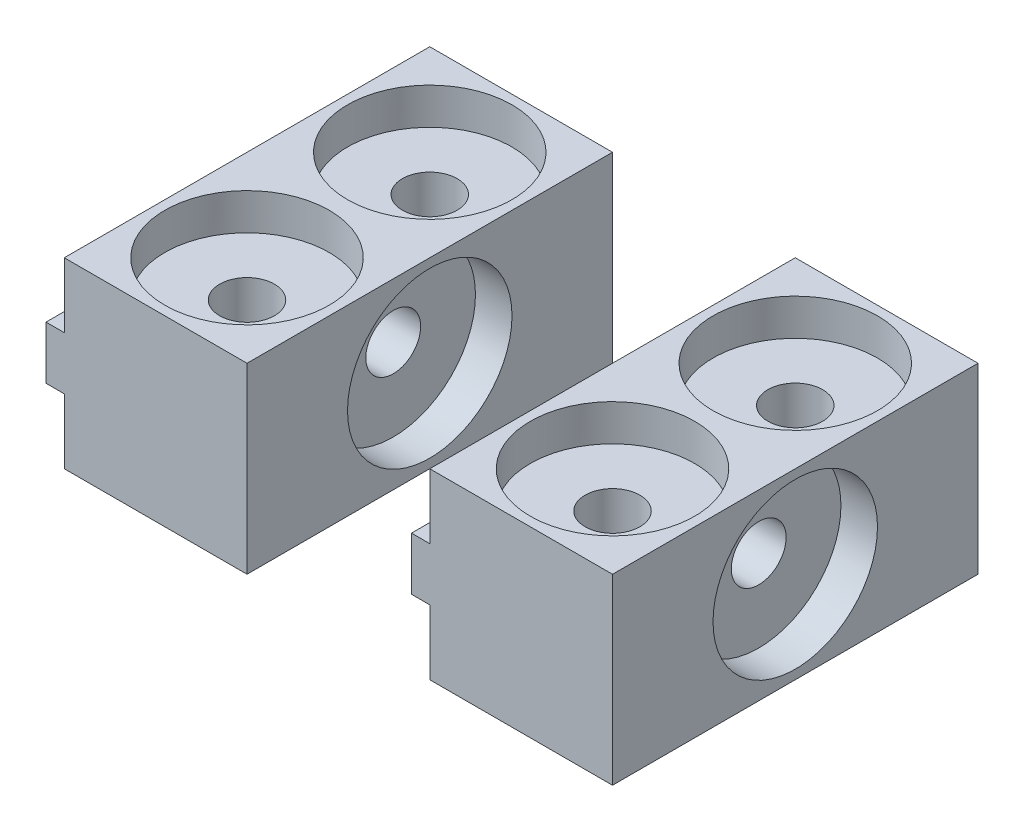
SolidWorks part; units mm, degrees
ref_plane "Front Plane" through (0, 0, 0) normal (0, 0, 1) x (1, 0, 0)
ref_plane "Top Plane" through (0, 0, 0) normal (0, 1, 0) x (1, 0, 0)
ref_plane "Right Plane" through (0, 0, 0) normal (1, 0, 0) x (0, 0, -1)
sketch "Sketch1" plane through (0, 0, 0) normal (0, 0, 1) x (1, 0, 0)
  line L0 (-10, 0) -> (-10, -3.55)
  line L1 (-10, -3.55) -> (-11, -3.55)
  line L2 (-11, -3.55) -> (-11, -6.45)
  line L3 (-11, -6.45) -> (-10, -6.45)
  line L4 (-10, -6.45) -> (-10, -10)
  line L5 (-10, -10) -> (0, -10)
  line L8 (0, -10) -> (0, 0)
  line L9 (0, 0) -> (-10, 0)
  dimension "D1" = 10
  dimension "D2" = 1
  dimension "D3" = 2.9
  dimension "D4" = 10
extrude "Boss-Extrude1" add sketch "Sketch1" along normal blind 20
sketch "Sketch2" plane through (0, 0, 0) normal (0, 1, 0) x (1, 0, 0)
  line L1 (-10, -20) -> (-10, 0) construction
  line L2 (0, -20) -> (-10, -20) construction
  circle A0 centre (-5, -15) radius 1.5
  dimension "D1" = 3
  dimension "D2" = 5
  dimension "D3" = 5
extrude "Cut-Extrude1" cut sketch "Sketch2" against normal through all
sketch "Sketch3" plane through (0, 0, 0) normal (1, 0, 0) x (0, 0, -1)
  line L0 (-20, -10) -> (-20, 0) construction
  circle A0 centre (-10, -5) radius 4.5
  dimension "D1" = 9
  dimension "D2" = 10
  dimension "D3" = 5
extrude "Cut-Extrude2" cut sketch "Sketch3" against normal blind 2
sketch "Sketch4" plane through (-2, 0, 0) normal (1, 0, 0) x (0, 0, -1)
  circle A0 centre (-10, -5) radius 1.5
  circle A1 centre (-10, -5) radius 4.5 construction
  dimension "D1" = 3
extrude "Cut-Extrude3" cut sketch "Sketch4" against normal through all
sketch "Sketch6" plane through (0, 0, 0) normal (0, 1, 0) x (1, 0, 0)
  circle A0 centre (-5, -15) radius 4.5
  circle A1 centre (-5, -15) radius 1.5 construction
  dimension "D1" = 9
extrude "Cut-Extrude4" cut sketch "Sketch6" against normal blind 2
pattern_linear "LPattern1" count 2 spacing 10 along (0, 0, -1) of "Cut-Extrude1", "Cut-Extrude4"
pattern_linear "LPattern3" count 2 spacing 20 along (-1, 0, 0) of bodies 105
